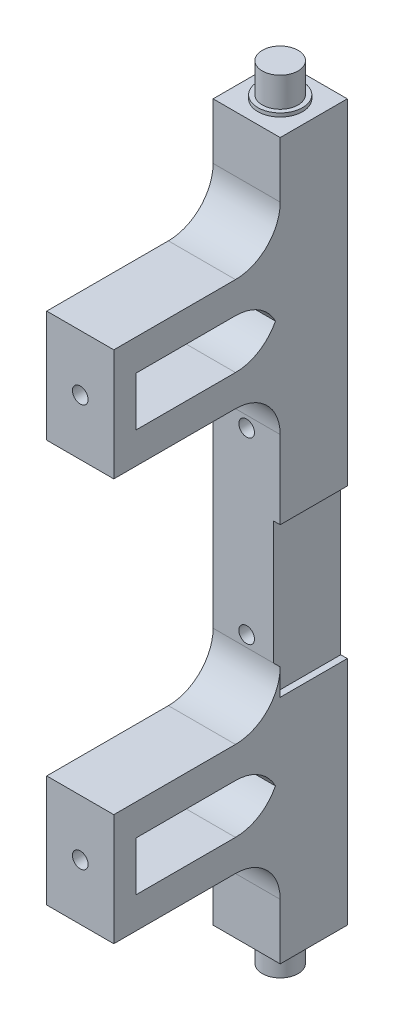
SolidWorks part; units mm, degrees
ref_plane "Plan de face" through (0, 0, 0) normal (1, 0, 0) x (0, 1, 0)
ref_plane "Plan de dessus" through (0, 0, 0) normal (0, 0, 1) x (0, 1, 0)
ref_plane "Plan de droite" through (0, 0, 0) normal (0, 1, 0) x (-1, 0, 0)
sketch "Esquisse1" plane through (0, 0, 0) normal (0, 0, 1) x (0, 1, 0)
  line L0 (0, 0) -> (-102.3211, 0) construction
  line L1 (-57.5, 7.5) -> (-32.5, 7.5)
  line L2 (-57.5, 7.5) -> (-57.5, -7.5)
  line L3 (-57.5, -7.5) -> (-32.5, -7.5)
  line L4 (-32.5, 7.5) -> (-32.5, -7.5)
  line L5 (-57.5, 7.5) -> (-32.5, -7.5) construction
  line L6 (-57.5, -7.5) -> (-32.5, 7.5) construction
  line L7 (0, 0) -> (0, -24.159) construction
  line L8 (57.5, -7.5) -> (32.5, -7.5)
  line L9 (32.5, 7.5) -> (32.5, -7.5)
  line L10 (57.5, 7.5) -> (32.5, 7.5)
  line L11 (57.5, 7.5) -> (57.5, -7.5)
  point P0 (-45, 0)
  dimension "D1" = 45
  dimension "D2" = 25
  dimension "D3" = 15
extrude "Boss.-Extru.1" add sketch "Esquisse1" along normal blind 37.2
sketch "Esquisse3" plane through (0, 0, 0) normal (0, 0, 1) x (0, 1, 0)
  line L1 (-80, -7.5) -> (80, -7.5)
  line L2 (-80, -7.5) -> (-80, 7.5)
  line L3 (-80, 7.5) -> (80, 7.5)
  line L4 (80, -7.5) -> (80, 7.5)
  line L5 (-80, -7.5) -> (80, 7.5) construction
  line L6 (-80, 7.5) -> (80, -7.5) construction
  point P0 (0, 0)
  dimension "D1" = 160
  dimension "D2" = 15
extrude "Boss.-Extru.2" add sketch "Esquisse3" against normal blind 15
sketch "Esquisse4" plane through (0, -80, 0) normal (0, -1, 0) x (-1, 0, 0)
  line L0 (-7.5, 0) -> (7.5, 15) construction
  line L1 (7.5, 15) -> (7.5, 0) construction
  line L2 (7.5, 0) -> (-7.5, 15) construction
  circle A0 centre (0, 7.5) radius 4
  circle A1 centre (0, 7.5) radius 5
  dimension "D1" = 10
extrude "Boss.-Extru.5" add sketch "Esquisse4" along normal blind 0.8 contours A0 | A1 region at (0, -80, -7.5)
extrude "Boss.-Extru.6" add sketch "Esquisse4<6>" along normal blind 7.4 contours A0 region at (0, -80, -7.5)
sketch "Esquisse4<6>" plane through (0, -80, 0) normal (0, -1, 0) x (-1, 0, 0) same geometry as "Esquisse4"
mirror "Symétrie2" about plane through (0, 0, 0) normal (0, 1, 0) of "Boss.-Extru.5", "Boss.-Extru.6"
fillet "Congé1" radius 10 4 edges at (0, -32.5, 0) (0, -57.5, 0) (0, 57.5, 0) (0, 32.5, 0)
sketch "Esquisse5" plane through (-7.5, 0, 0) normal (-1, 0, 0) x (0, -1, 0)
  line L0 (0, 0) -> (0, 29.4885) construction
  line L2 (32.5, 37.2) -> (57.5, 37.2) construction
  line L3 (39.5, 32.2) -> (50.5, 32.2)
  line L4 (39.5, 32.2) -> (39.5, 0)
  line L5 (39.5, 0) -> (50.5, 0)
  line L6 (50.5, 32.2) -> (50.5, 0)
  line L7 (32.5, 37.2) -> (32.5, 10) construction
  line L8 (57.5, 37.2) -> (57.5, 10) construction
  line L9 (-80, -15) -> (80, -15) construction
  line L10 (-50.5, 32.2) -> (-50.5, 0)
  line L11 (-39.5, 0) -> (-50.5, 0)
  line L12 (-39.5, 32.2) -> (-39.5, 0)
  line L13 (-39.5, 32.2) -> (-50.5, 32.2)
  dimension "D1" = 5
  dimension "D2" = 7
  dimension "D3" = 7
  dimension "D4" = 11
  dimension "D5" = 15
extrude "Enlèv. mat.-Extru.1" cut sketch "Esquisse5" against normal through all
fillet "Congé2" radius 10 4 edges at (0, 39.5, 0) (0, 50.5, 0) (0, -39.5, 0) (0, -50.5, 0)
sketch "Esquisse6" plane through (0, 0, 32.2) normal (0, 0, -1) x (1, 0, 0)
  line L0 (0, 0) -> (-5.7044, 0) construction
  line L1 (0, 0) -> (0, 13.0401) construction
  line L2 (-7.5, 57.5) -> (7.5, 57.5) construction
  line L3 (7.5, 32.5) -> (-7.5, 32.5) construction
  line L4 (7.5, 32.5) -> (-7.5, 32.5) construction
  circle A0 centre (0, 45) radius 1.75
  circle A1 centre (0, -45) radius 1.75
  dimension "D2" = 12.5
  dimension "D3" = 3.5
  dimension "D4" = 90
  dimension "D1" = 25
extrude "Enlèv. mat.-Extru.2" cut sketch "Esquisse6" against normal through all
sketch "Esquisse7" plane through (0, 0, 0) normal (0, 0, 1) x (1, 0, 0)
  line L9 (-7.5, 22.5) -> (-27.5, 22.5)
  line L10 (-27.5, 22.5) -> (-27.5, -22.5)
  line L11 (-27.5, -22.5) -> (-7.5, -22.5)
  line L12 (-7.5, -22.5) -> (-7.5, -12.5)
  line L13 (-7.5, 22.5) -> (-7.5, -22.5) construction
  line L14 (-7.5, -12.5) -> (-17.5, -12.5)
  line L15 (-17.5, -12.5) -> (-17.5, 12.5)
  line L16 (-17.5, 12.5) -> (-7.5, 12.5)
  line L21 (-7.5, 22.5) -> (-7.5, -22.5)
  line L22 (-7.5, -22.5) -> (7.5, -22.5)
  line L23 (7.5, -22.5) -> (7.5, 22.5)
  line L24 (7.5, 22.5) -> (-7.5, 22.5)
  line L25 (-7.5, 22.5) -> (-7.5, 12.5)
  dimension "D1" = 10
  dimension "D2" = 10
  dimension "D3" = 10
  dimension "D4" = 25
  dimension "D5" = 10
  dimension "D6" = 0
extrude "Boss.-Extru.8" [suppressed] add sketch "Esquisse7" against normal blind 15
sketch "Esquisse8" [suppressed] plane through (0, 0, 0) normal (0, 0, 1) x (1, 0, 0)
  line L0 (-7.5, -12.5) -> (-17.5, -12.5) construction
  line L1 (-7.5, 12.5) -> (36.6313, 12.5)
  line L2 (-7.5, 12.5) -> (-7.5, -12.5)
  line L3 (-7.5, -12.5) -> (36.6313, -12.5)
  line L4 (36.6313, 12.5) -> (36.6313, -12.5)
extrude "Enlèv. mat.-Extru.3" [suppressed] cut sketch "Esquisse8" against normal through all
fillet "Congé3" [suppressed] radius 7
sketch "Esquisse10" [suppressed] plane through (0, 0, 0) normal (0, 0, 1) x (1, 0, 0)
  line L0 (-27.5, 15.5) -> (-27.5, -15.5) construction
  line L4 (-22.5, 0) -> (-22.5, 5.692) construction
  line L7 (-3.5, 17.5) -> (-5.9374, 17.5) construction
  line L8 (-14.5, 22.5) -> (-20.5, 22.5) construction
  line L9 (-10.5, -17.5) -> (-14.5, -17.5) construction
  line L10 (-10.5, 12.5) -> (0.5, 12.5) construction
  line L11 (-17.5, -5.5) -> (-17.5, 5.5) construction
  circle A0 centre (-22.5, 17.5) radius 1.75
  circle A1 centre (-22.5, -17.5) radius 1.75
  dimension "D1" = 3.5
  dimension "D2" = 3.5
  dimension "D3" = 5
  dimension "D4" = 5
  dimension "D5" = 5
  dimension "D6" = 5
extrude "Enlèv. mat.-Extru.4" [suppressed] cut sketch "Esquisse10" against normal through all
ref_plane "Plan1" through (7.5, 32.5, 37.2) normal (0, 0, -1) x (-1, 0, 0)
sketch "Esquisse11" plane through (0, 0, 0) normal (0, 0, 1) x (0, 1, 0)
  circle A0 centre (20, 0) radius 1.75
  circle A1 centre (-20, 0) radius 1.75
extrude "Trous vis support capteurs" cut sketch "Esquisse11" against normal through all
sketch "Esquisse12" plane through (0, 0, 0) normal (0, 0, 1) x (0, 1, 0)
  line L1 (5.024, -6.0385) -> (-28.376, -6.0385)
  line L2 (5.024, -6.0385) -> (5.024, -10.7385)
  line L3 (5.024, -10.7385) -> (-28.376, -10.7385)
  line L4 (-28.376, -6.0385) -> (-28.376, -10.7385)
extrude "Encoche carte capteur" cut sketch "Esquisse12" against normal through all
